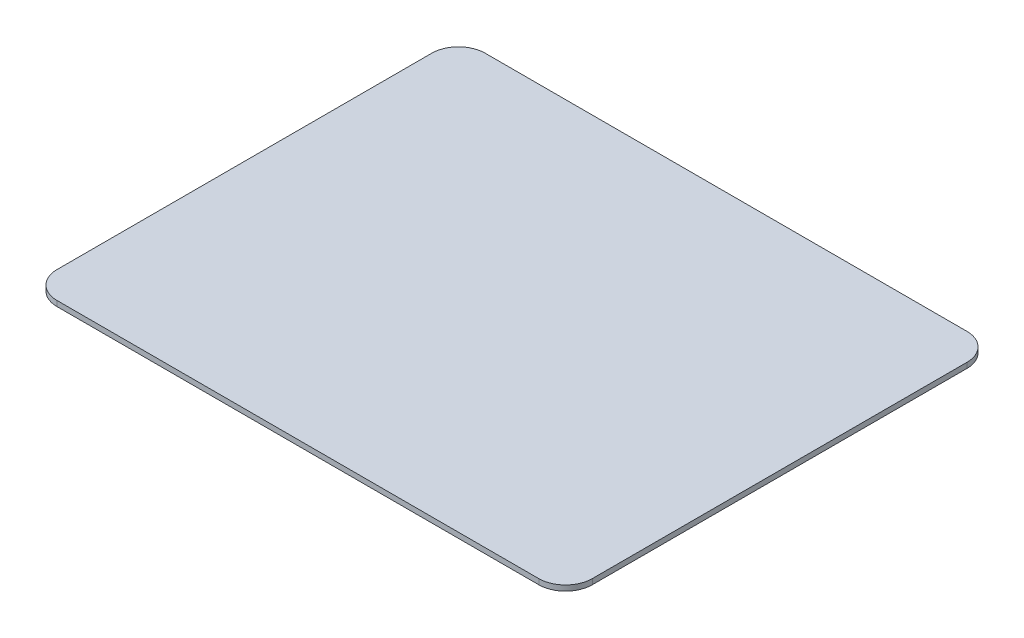
SolidWorks part; units mm, degrees
ref_plane "Front Plane" through (0, 0, 0) normal (0, 0, 1) x (1, 0, 0)
ref_plane "Top Plane" through (0, 0, 0) normal (0, 1, 0) x (1, 0, 0)
ref_plane "Right Plane" through (0, 0, 0) normal (1, 0, 0) x (0, 0, -1)
sketch "Sketch1" plane through (0, 0, 0) normal (0, 1, 0) x (1, 0, 0)
  line L1 (-114.3, -101.6) -> (114.3, -101.6)
  line L2 (-127, -88.9) -> (-127, 88.9)
  line L3 (-114.3, 101.6) -> (114.3, 101.6)
  line L4 (127, -88.9) -> (127, 88.9)
  line L5 (-127, -101.6) -> (127, 101.6) construction
  line L6 (-127, 101.6) -> (127, -101.6) construction
  arc A0 (127, 88.9) -> (114.3, 101.6) centre (114.3, 88.9) ccw
  arc A1 (114.3, -101.6) -> (127, -88.9) centre (114.3, -88.9) ccw
  arc A2 (-127, -88.9) -> (-114.3, -101.6) centre (-114.3, -88.9) ccw
  arc A3 (-127, 88.9) -> (-114.3, 101.6) centre (-114.3, 88.9) cw
  point P0 (0, 0)
  dimension "D3" = 12.7
  dimension "D1" = 254
  dimension "D2" = 203.2
extrude "Boss-Extrude1" add sketch "Sketch1" along normal blind 2.54
